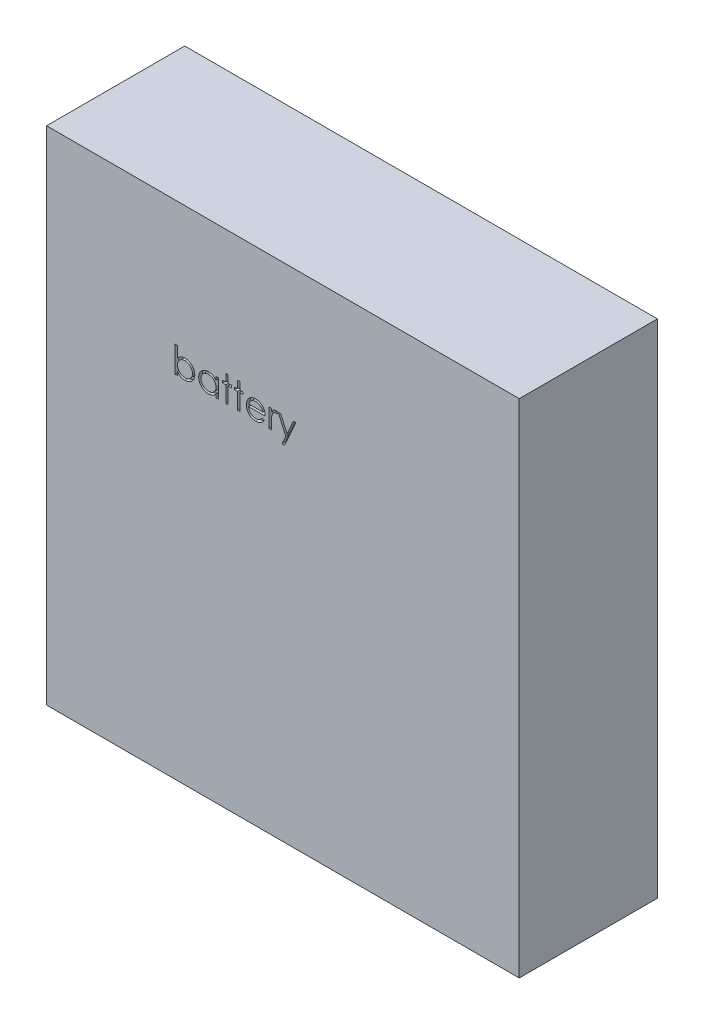
SolidWorks part; units mm, degrees
ref_plane "Front Plane" through (0, 0, 0) normal (0, 0, 1) x (1, 0, 0)
ref_plane "Top Plane" through (0, 0, 0) normal (0, 1, 0) x (1, 0, 0)
ref_plane "Right Plane" through (0, 0, 0) normal (1, 0, 0) x (0, 0, -1)
sketch "Sketch1" plane through (0, 0, 0) normal (0, 0, 1) x (1, 0, 0)
  line L1 (0, 0) -> (65, 0)
  line L2 (0, 0) -> (0, 69)
  line L3 (0, 69) -> (65, 69)
  line L4 (65, 0) -> (65, 69)
  dimension "D1" = 65
  dimension "D2" = 69
extrude "Boss-Extrude1" add sketch "Sketch1" along normal blind 19
sketch "Sketch2" plane through (0, 0, 19) normal (0, 0, 1) x (1, 0, 0)
  text T0 "battery\r\n"
extrude "Cut-Extrude1" cut sketch "Sketch2" against normal blind 0.5
